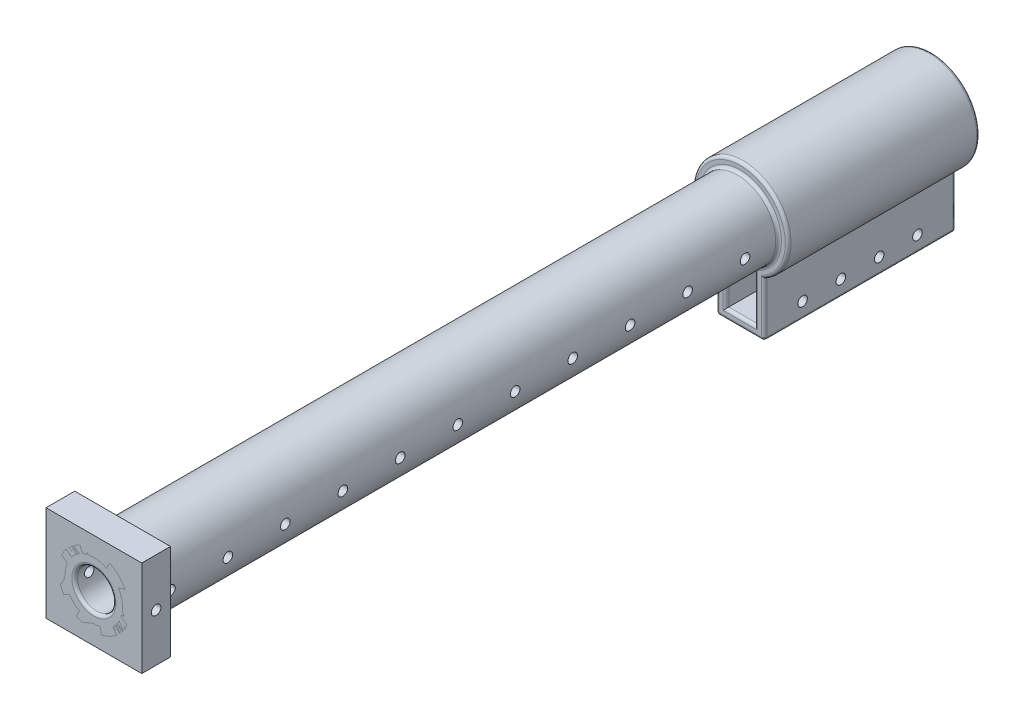
SolidWorks part; units mm, degrees
ref_plane "Front Plane" through (0, 0, 0) normal (0, 0, 1) x (1, 0, 0)
ref_plane "Top Plane" through (0, 0, 0) normal (0, 1, 0) x (1, 0, 0)
ref_plane "Right Plane" through (0, 0, 0) normal (1, 0, 0) x (0, 0, -1)
sketch "Sketch1" plane through (0, 0, 0) normal (0, 0, 1) x (1, 0, 0)
  line L0 (7.5, -18.5405) -> (7.5, -45)
  line L1 (7.5, -45) -> (-7.5, -45)
  line L2 (-7.5, -45) -> (-7.5, -18.5405)
  line L3 (0, 0) -> (0, -54.3382) construction
  line L4 (12.5, -21.6506) -> (12.5, -50)
  line L5 (12.5, -50) -> (-12.5, -50)
  line L6 (-12.5, -50) -> (-12.5, -21.6506)
  arc A0 (7.5, -18.5405) -> (-7.5, -18.5405) centre (0, 0) ccw
  arc A1 (12.5, -21.6506) -> (-12.5, -21.6506) centre (0, 0) ccw
  dimension "D1" = 40
  dimension "D2" = 15
  dimension "D3" = 45
  dimension "D4" = 5
extrude "Boss-Extrude1" add sketch "Sketch1" along normal blind 100
sketch "Sketch2" plane through (0, 0, 0) normal (0, 0, -1) x (-1, 0, 0)
  line L0 (7.5, -45) -> (-7.5, -45) construction
  line L1 (7.5, -18.5405) -> (7.5, -45) construction
  line L2 (-7.5, -45) -> (-7.5, -18.5405) construction
  line L3 (7.5, -45) -> (-7.5, -45)
  line L4 (7.5, -18.5405) -> (7.5, -45)
  line L5 (-7.5, -45) -> (-7.5, -18.5405)
  arc A0 (7.5, -18.5405) -> (-7.5, -18.5405) centre (0, 0) ccw construction
  arc A1 (7.5, -18.5405) -> (-7.5, -18.5405) centre (0, 0) ccw
extrude "Boss-Extrude2" add sketch "Sketch2" against normal blind 10
sketch "Sketch3" plane through (0, 0, 10) normal (0, 0, 1) x (1, 0, 0)
  circle A0 centre (0, 0) radius 20
  circle A1 centre (0, 0) radius 10
  dimension "D1" = 40
  dimension "D2" = 20
extrude "Boss-Extrude3" add sketch "Sketch3" along normal blind 427.5
fillet "Fillet1" radius 1.5 14 edges at (7.5, -18.5405, 55) (-7.5, -18.5405, 55) (-12.5, -35.8253, 0) (0, -50, 0) (12.5, -35.8253, 0) (0, 25, 0) (0, -45, 100) (7.5, -31.7702, 100) (0, 20, 100) (-7.5, -31.7702, 100) (12.5, -35.8253, 100) (0, -50, 100) (-12.5, -35.8253, 100) (0, 25, 100)
fillet "Fillet2" radius 1.5 6 edges at (12.0607, -49.5607, 99.5607) (12.0607, -49.5607, 0.4393) (-12.0607, -49.5607, 99.5607) (-12.0607, -49.5607, 0.4393) (12.5, -50, 50) (-12.5, -50, 50)
fillet "Fillet3" radius 1.5 2 edges at (10, 0, 437.5) (20, 0, 437.5)
sketch "Sketch4" plane through (0, 0, 0) normal (1, 0, 0) x (0, 0, -1)
  line L0 (-437.5, 18.5) -> (-437.5, -18.5) construction
  circle A0 centre (-417.5, 0) radius 2.5
  circle A1 centre (-387.5, 0) radius 2.5
  circle A2 centre (-357.5, 0) radius 2.5
  circle A3 centre (-327.5, 0) radius 2.5
  circle A4 centre (-297.5, 0) radius 2.5
  circle A5 centre (-267.5, 0) radius 2.5
  circle A6 centre (-237.5, 0) radius 2.5
  circle A7 centre (-207.5, 0) radius 2.5
  circle A8 centre (-177.5, 0) radius 2.5
  circle A9 centre (-147.5, 0) radius 2.5
  circle A10 centre (-117.5, 0) radius 2.5
  dimension "D1" = 5
  dimension "D2" = 20
  dimension "D4" = 30
  dimension "D3" = 11
extrude "Cut-Extrude1" cut sketch "Sketch4" against normal through all both and the other way through all
sketch "Sketch5" plane through (12.5, 0, 0) normal (1, 0, 0) x (0, 0, -1)
  line L0 (0, -20.7666) -> (0, -48.5) construction
  line L1 (-98.5, -21.6506) -> (-1.5, -21.6506) construction
  circle A0 centre (-20, -41.6506) radius 2.5
  circle A1 centre (-40, -41.6506) radius 2.5
  circle A2 centre (-60, -41.6506) radius 2.5
  circle A3 centre (-80, -41.6506) radius 2.5
  dimension "D1" = 5
  dimension "D2" = 20
  dimension "D4" = 20
  dimension "D5" = 20
  dimension "D3" = 4
extrude "Cut-Extrude2" cut sketch "Sketch5" against normal through all both and the other way through all
sketch "Sketch6" plane through (0, 0, 437.5) normal (0, 0, 1) x (1, 0, 0)
  line L0 (-25, 25) -> (25, -25) construction
  line L1 (-25, 25) -> (25, 25)
  line L2 (-25, 25) -> (-25, -25)
  line L3 (-25, -25) -> (25, -25)
  line L4 (25, 25) -> (25, -25)
  circle A0 centre (0, 0) radius 15
  point P4 (0, 0)
  dimension "D3" = 30
  dimension "D1" = 50
  dimension "D2" = 50
extrude "Boss-Extrude4" add sketch "Sketch6" against normal blind 15 separate body
sketch "Sketch7" plane through (25, 0, 0) normal (1, 0, 0) x (0, 0, -1)
  line L0 (-422.5, 25) -> (-437.5, -25) construction
  circle A0 centre (-430, 0) radius 2.5
  dimension "D1" = 5
extrude "Cut-Extrude3" cut sketch "Sketch7" against normal through all
